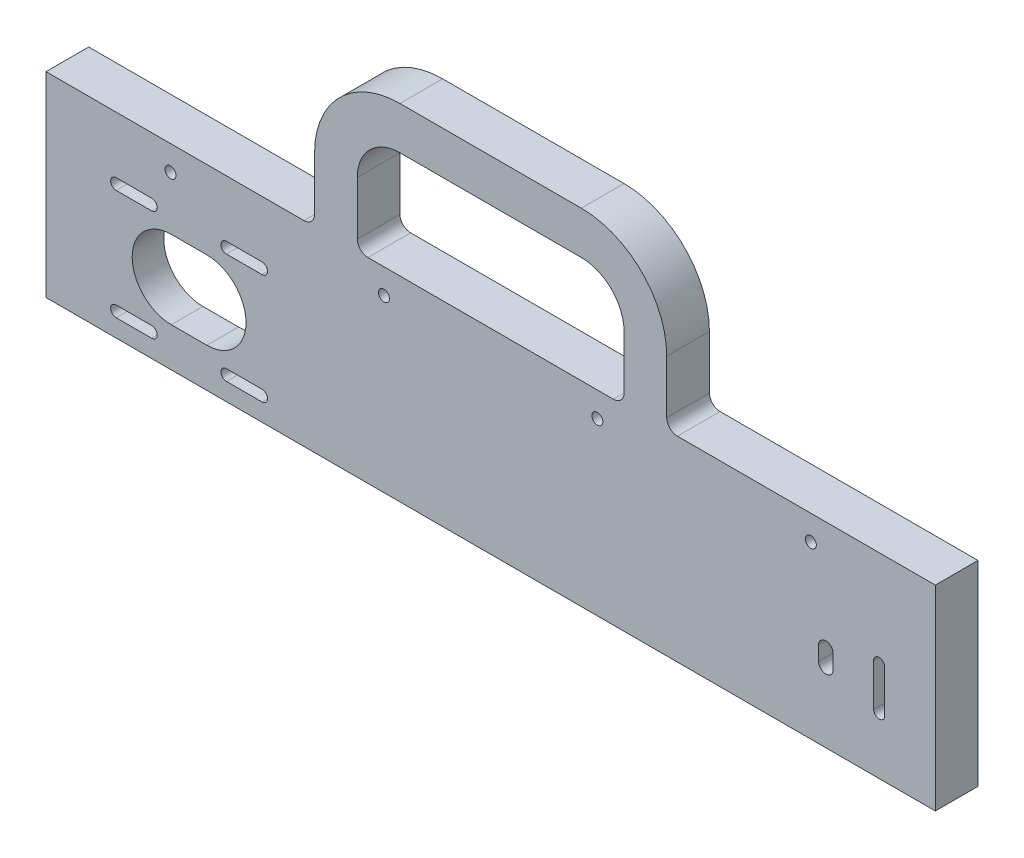
SolidWorks part; units mm, degrees
ref_plane "Ebene vorne" through (0, 0, 0) normal (0, 0, 1) x (1, 0, 0)
ref_plane "Ebene oben" through (0, 0, 0) normal (0, 1, 0) x (1, 0, 0)
ref_plane "Ebene rechts" through (0, 0, 0) normal (1, 0, 0) x (0, 0, -1)
sketch "Skizze2" plane through (0, 0, 0) normal (0, 0, 1) x (1, 0, 0)
  line L0 (-90, 20.5) -> (90, 20.5) construction
  line L5 (-125, -27.5) -> (125, -27.5)
  line L6 (-125, -27.5) -> (-125, 27.5)
  line L8 (125, -27.5) -> (125, 27.5)
  line L9 (-125, -27.5) -> (125, 27.5) construction
  line L10 (-125, 27.5) -> (125, -27.5) construction
  line L11 (-84.775, -5.5) -> (101.725, -5.5) construction
  line L12 (-100.275, -21) -> (-69.275, -21) construction
  line L13 (-100.275, -21) -> (-100.275, 10) construction
  line L14 (-100.275, 10) -> (-69.275, 10) construction
  line L15 (-69.275, -21) -> (-69.275, 10) construction
  line L16 (-100.275, -21) -> (-69.275, 10) construction
  line L17 (-100.275, 10) -> (-69.275, -21) construction
  line L18 (109.225, 0.45) -> (109.225, -11.45) construction
  line L19 (94.225, -13) -> (109.225, -13) construction
  line L20 (94.225, -13) -> (94.225, 2) construction
  line L21 (94.225, 2) -> (109.225, 2) construction
  line L22 (109.225, -13) -> (109.225, 2) construction
  line L23 (94.225, -13) -> (109.225, 2) construction
  line L24 (94.225, 2) -> (109.225, -13) construction
  line L25 (110.775, 0.45) -> (110.775, -11.45)
  line L26 (107.675, 0.45) -> (107.675, -11.45)
  line L27 (94.225, -3.5) -> (94.225, -7.5) construction
  line L28 (96.275, -3.5) -> (96.275, -7.5)
  line L29 (92.175, -3.5) -> (92.175, -7.5)
  line L30 (-64.275, 10) -> (-74.275, 10) construction
  line L31 (-64.275, 8.45) -> (-74.275, 8.45)
  line L32 (-64.275, 11.55) -> (-74.275, 11.55)
  line L33 (-105.275, 10) -> (-95.275, 10) construction
  line L34 (-105.275, 11.55) -> (-95.275, 11.55)
  line L35 (-105.275, 8.45) -> (-95.275, 8.45)
  line L36 (-105.275, -21) -> (-95.275, -21) construction
  line L37 (-105.275, -19.45) -> (-95.275, -19.45)
  line L38 (-105.275, -22.55) -> (-95.275, -22.55)
  line L39 (-64.275, -21) -> (-74.275, -21) construction
  line L40 (-64.275, -22.55) -> (-74.275, -22.55)
  line L41 (-64.275, -19.45) -> (-74.275, -19.45)
  line L42 (-79.775, -5.5) -> (-89.775, -5.5) construction
  line L43 (-79.775, -16.5) -> (-89.775, -16.5)
  line L44 (-79.775, 5.5) -> (-89.775, 5.5)
  line L45 (-125, 27.5) -> (-49.5, 27.5)
  line L46 (-110.775, 15.5) -> (-58.775, 15.5)
  line L47 (-110.775, 15.5) -> (-110.775, -27.5)
  line L48 (-110.775, -27.5) -> (-58.775, -27.5)
  line L49 (-58.775, 15.5) -> (-58.775, -27.5)
  line L53 (-49.5, 27.5) -> (-49.5, 69.5)
  line L54 (-49.5, 69.5) -> (49.5, 69.5)
  line L55 (49.5, 27.5) -> (49.5, 69.5)
  line L56 (-37.5, 27.5) -> (37.5, 27.5)
  line L57 (-37.5, 27.5) -> (-37.5, 57.5)
  line L58 (-37.5, 57.5) -> (37.5, 57.5)
  line L59 (37.5, 27.5) -> (37.5, 57.5)
  line L60 (49.5, 27.5) -> (125, 27.5)
  line L61 (110.775, 0.45) -> (-110.775, 0.45) construction
  circle A4 centre (-90, 20.5) radius 1.55
  circle A5 centre (90, 20.5) radius 1.55
  arc A11 (110.775, 0.45) -> (107.675, 0.45) centre (109.225, 0.45) ccw
  arc A12 (107.675, -11.45) -> (110.775, -11.45) centre (109.225, -11.45) ccw
  arc A13 (96.275, -3.5) -> (92.175, -3.5) centre (94.225, -3.5) ccw
  arc A14 (92.175, -7.5) -> (96.275, -7.5) centre (94.225, -7.5) ccw
  arc A15 (-64.275, 8.45) -> (-64.275, 11.55) centre (-64.275, 10) ccw
  arc A16 (-74.275, 11.55) -> (-74.275, 8.45) centre (-74.275, 10) ccw
  arc A17 (-105.275, 11.55) -> (-105.275, 8.45) centre (-105.275, 10) ccw
  arc A18 (-95.275, 8.45) -> (-95.275, 11.55) centre (-95.275, 10) ccw
  arc A19 (-105.275, -19.45) -> (-105.275, -22.55) centre (-105.275, -21) ccw
  arc A20 (-95.275, -22.55) -> (-95.275, -19.45) centre (-95.275, -21) ccw
  arc A21 (-64.275, -22.55) -> (-64.275, -19.45) centre (-64.275, -21) ccw
  arc A22 (-74.275, -19.45) -> (-74.275, -22.55) centre (-74.275, -21) ccw
  arc A23 (-79.775, -16.5) -> (-79.775, 5.5) centre (-79.775, -5.5) ccw
  arc A24 (-89.775, 5.5) -> (-89.775, -16.5) centre (-89.775, -5.5) ccw
  circle A25 centre (-30, 20.5) radius 1.55
  circle A26 centre (30, 20.5) radius 1.55
  point P0 (0, 0)
  point P8 (0, 20.5)
  point P14 (-84.775, 15.5)
  point P23 (101.725, -5.5)
  point P30 (109.225, -5.5)
  point P35 (94.225, -5.5)
  point P44 (-69.275, 10)
  point P50 (-100.275, 10)
  point P57 (-100.275, -21)
  point P64 (-69.275, -21)
  point P71 (-84.775, -5.5)
  point P80 (0, 69.5)
  point P85 (0, 57.5)
  point P86 (-49.5, 48.5)
  point P89 (0, 0.45)
  point P94 (-110.775, -27.5)
  dimension "D3" = 180
  dimension "D5" = 3.1
  dimension "D8" = 15
  dimension "D13" = 3.1
  dimension "D9" = 3.1
  dimension "D10" = 15
  dimension "D11" = 4.1
  dimension "D31" = 3.1
  dimension "D32" = 3.1
  dimension "D2" = 250
  dimension "D4" = 7
  dimension "D6" = 31
  dimension "D7" = 31
  dimension "D12" = 4
  dimension "D14" = 3.1
  dimension "D15" = 3.1
  dimension "D16" = 5
  dimension "D17" = 5
  dimension "D18" = 5
  dimension "D19" = 5
  dimension "D20" = 5
  dimension "D21" = 179
  dimension "D22" = 22
  dimension "D23" = 22
  dimension "D24" = 26
  dimension "D25" = 21
  dimension "D26" = 52
  dimension "D27" = 12
  dimension "D28" = 12
  dimension "D29" = 30
  dimension "D30" = 75
  dimension "D33" = 30
  dimension "D34" = 30
extrude "Aufsatz-Linear austragen1" add sketch "Skizze2" along normal blind 12 contours L5 L8 L6 A14 L29 A13 L28 A12 L26 A11 L25 A5 A4 L46 L49 L48 L47 | L49 L46 L47 L48 A24 L44 A23 L43 A22 L41 A21 L40 A20 L38 A19 L37 A18 L35 A17 L34 A16 L32 A15 L31 region at (13.6595, 8.9536, 0) region at (-110.1002, -6, 0)
extrude "Schnitt-Linear austragen1" cut sketch "Skizze2<3>" along normal blind 3.11 contours L49 L46 L47 L48 A24 L44 A23 L43 A22 L41 A21 L40 A20 L38 A19 L37 A18 L35 A17 L34 A16 L32 A15 L31 region at (-110.1002, -6, 0)
sketch "Skizze2<3>" plane through (0, 0, 0) normal (0, 0, 1) x (1, 0, 0) same geometry as "Skizze2"
fillet "Verrundung1" radius 12 2 edges at (37.5, 57.5, 6) (-37.5, 57.5, 6)
fillet "Verrundung2" radius 24 2 edges at (49.5, 69.5, 6) (-49.5, 69.5, 6)
fillet "Verrundung3" radius 3 4 edges at (49.5, 27.5, 6) (-37.5, 27.5, 6) (37.5, 27.5, 6) (-49.5, 27.5, 6)
fillet "Verrundung4" radius 3 2 edges at (-110.775, 15.5, 1.555) (-58.775, 15.5, 1.555)
